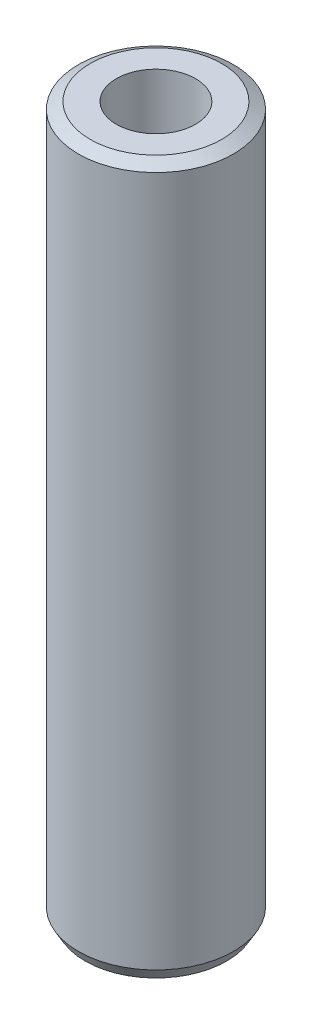
SolidWorks part; units mm, degrees
ref_plane "Front Plane" through (0, 0, 0) normal (0, 0, 1) x (1, 0, 0)
ref_plane "Top Plane" through (0, 0, 0) normal (0, 1, 0) x (1, 0, 0)
ref_plane "Right Plane" through (0, 0, 0) normal (1, 0, 0) x (0, 0, -1)
sketch "Sketch1" plane through (0, 0, 0) normal (0, 1, 0) x (1, 0, 0)
  circle A0 centre (0, 0) radius 7.5
  dimension "SHAFT_OD" = 15
extrude "Boss-Extrude1" add sketch "Sketch1" along normal blind 68.5968
sketch "Sketch2" plane through (0, 0, 0) normal (0, 1, 0) x (1, 0, 0)
  circle A0 centre (0, 0) radius 3.8294
  dimension "BORE_D" = 7.6588
extrude "Cut-Extrude1" cut sketch "Sketch2" along normal through all
chamfer "Chamfer1" distance 0.6565 angle 60 2 edges at (0, 68.5968, 7.5) (0, 0, 7.5) first distance on face at (0, 68.5968, 7.5) first distance on face at (0, 0, 3.8294)
